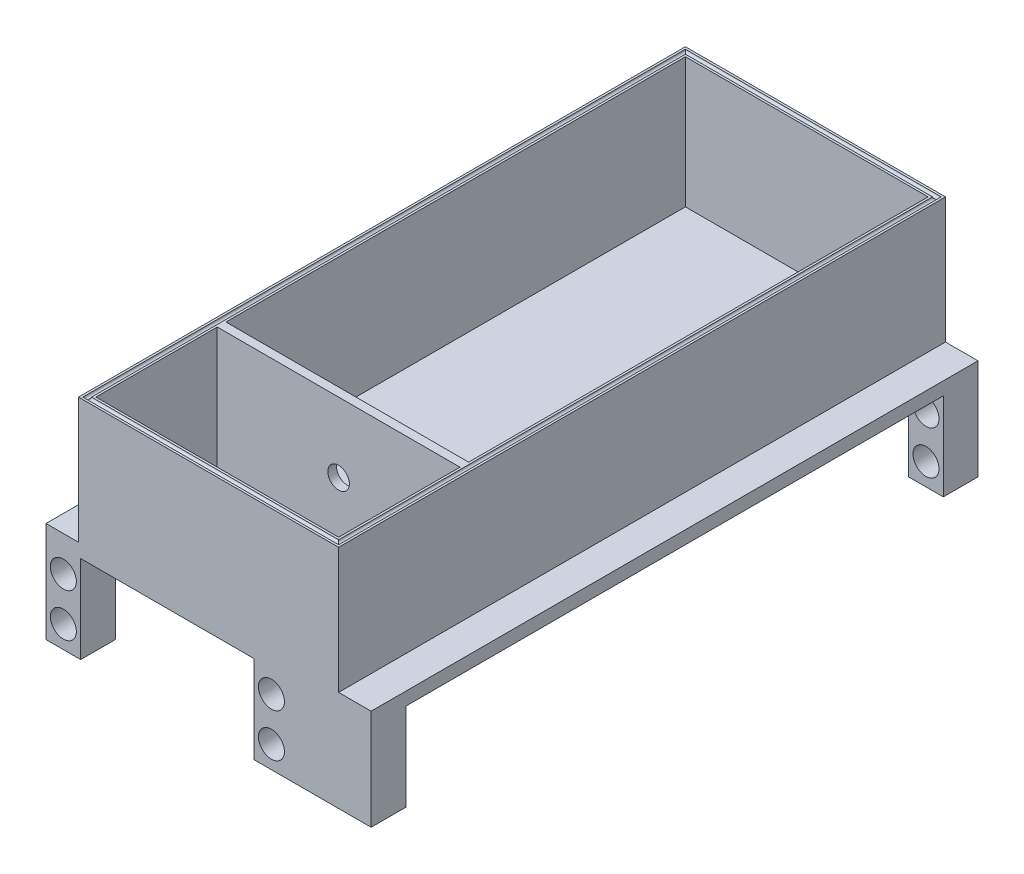
SolidWorks part; units mm, degrees
ref_plane "Front Plane" through (0, 0, 0) normal (0, 0, 1) x (1, 0, 0)
ref_plane "Top Plane" through (0, 0, 0) normal (0, 1, 0) x (1, 0, 0)
ref_plane "Right Plane" through (0, 0, 0) normal (1, 0, 0) x (0, 0, -1)
sketch "Sketch1" plane through (0, 0, 0) normal (0, 1, 0) x (1, 0, 0)
  line L1 (-30, 55) -> (30, 55)
  line L2 (-30, 55) -> (-30, -55)
  line L3 (-30, -55) -> (30, -55)
  line L4 (30, 55) -> (30, -55)
  line L5 (-30, 55) -> (30, -55) construction
  line L6 (-30, -55) -> (30, 55) construction
  point P0 (0, 0)
  dimension "D1" = 110
  dimension "D2" = 60
extrude "Boss-Extrude1" add sketch "Sketch1" along normal blind 2
sketch "Sketch2" plane through (0, 2, 0) normal (0, 1, 0) x (1, 0, 0)
  line L0 (-28, 53) -> (-28, -53)
  line L1 (-28, -53) -> (28, -53)
  line L2 (28, -53) -> (28, 53)
  line L3 (28, 53) -> (-28, 53)
  line L4 (30, -55) -> (30, 55)
  line L5 (30, 55) -> (-30, 55)
  line L6 (-30, 55) -> (-30, -55)
  line L7 (-30, -55) -> (30, -55)
  line L8 (30, -55) -> (30, 55)
  line L9 (30, 55) -> (-30, 55)
  line L10 (-30, 55) -> (-30, -55)
  line L11 (-30, -55) -> (30, -55)
  dimension "D1" = 0
  dimension "D2" = 2
extrude "Boss-Extrude2" add sketch "Sketch2" along normal blind 30
sketch "Sketch3" plane through (0, 0, 0) normal (0, 1, 0) x (1, 0, 0)
  line L0 (-30, -55) -> (30, -55) construction
  line L1 (-30, -55) -> (30, -55)
  line L2 (-30, -55) -> (-30, -85)
  line L3 (-30, -85) -> (30, -85)
  line L4 (30, -55) -> (30, -85)
  line L5 (30, -55) -> (30, 55) construction
  line L6 (-30, 55) -> (-30, -55) construction
  dimension "D2" = 30
extrude "Boss-Extrude3" add sketch "Sketch3" along normal blind 2
sketch "Sketch4" plane through (0, 2, 0) normal (0, 1, 0) x (1, 0, 0)
  line L4 (-28, -55) -> (-30, -55)
  line L8 (-28, -57) -> (-28, -83)
  line L9 (-28, -83) -> (28, -83)
  line L10 (28, -83) -> (28, -57)
  line L11 (28, -57) -> (-28, -57)
  line L12 (-28, -55) -> (-28, -83)
  line L13 (-28, -83) -> (28, -83)
  line L14 (28, -83) -> (28, -55)
  line L16 (-30, -55) -> (-30, -85)
  line L17 (-30, -85) -> (30, -85)
  line L18 (30, -85) -> (30, -55)
  line L19 (30, -55) -> (-30, -55)
  line L20 (-30, -55) -> (-30, -85)
  line L21 (-30, -85) -> (30, -85)
  line L22 (30, -85) -> (30, -55)
  line L23 (30, -55) -> (28, -55)
  dimension "D1" = 2
  dimension "D2" = 0
extrude "Boss-Extrude4" add sketch "Sketch4" along normal blind 30
sketch "Sketch5" plane through (0, 0, 55) normal (0, 0, 1) x (1, 0, 0)
  circle A0 centre (0, 15.8909) radius 2.4868
extrude "Cut-Extrude1" cut sketch "Sketch5" against normal blind 30
sketch "Sketch6" plane through (0, 32, 0) normal (0, 1, 0) x (1, 0, 0)
  line L17 (-29, 54) -> (-29, -84)
  line L18 (-29, -84) -> (29, -84)
  line L19 (29, -84) -> (29, 54)
  line L22 (29, 54) -> (-29, 54)
  line L25 (-29, 54) -> (-29, -84)
  line L26 (-29, -84) -> (29, -84)
  line L27 (29, -84) -> (29, 54)
  line L30 (29, 54) -> (-29, 54)
  dimension "D1" = 1
sweep "Cut-Sweep1" cut path "Sketch6" circular profile diameter 1 parameters "D3"=1
sketch "Sketch43" plane through (0, 0, 0) normal (0, -1, 0) x (1, 0, 0)
  line L11 (30, -55) -> (37.5, -55)
  line L12 (37.5, -55) -> (37.5, 85)
  line L13 (37.5, 85) -> (30, 85)
  line L14 (-30, -55) -> (-37.5, -55)
  line L15 (-37.5, -55) -> (-37.5, 85)
  line L16 (-37.5, 85) -> (-30, 85)
  line L18 (-30, 55) -> (-30, -55)
  line L19 (-30, 55) -> (-30, 85)
  line L21 (30, -55) -> (30, 85)
  dimension "D1" = 7.5
  dimension "D2" = 7.5
extrude "Boss-Extrude7" add sketch "Sketch43" against normal blind 3 contours L13 L21 L11 L12 | L16 L19 L18 L14 L15
sketch "Sketch55" plane through (0, 0, 0) normal (0, -1, 0) x (1, 0, 0)
  line L0 (-37.5, 85) -> (37.5, 85) construction
  line L1 (-37.5, 85) -> (-29.5, 85)
  line L2 (-37.5, 85) -> (-37.5, 77)
  line L3 (-37.5, 77) -> (-29.5, 77)
  line L4 (-29.5, 85) -> (-29.5, 77)
  line L5 (10.5, 85) -> (37.5, 85)
  line L6 (10.5, 85) -> (10.5, 77)
  line L7 (10.5, 77) -> (37.5, 77)
  line L8 (37.5, 85) -> (37.5, 77)
  line L9 (37.5, -55) -> (-37.5, -55) construction
  line L10 (37.5, -55) -> (29.5, -55)
  line L11 (37.5, -55) -> (37.5, -47)
  line L12 (37.5, -47) -> (29.5, -47)
  line L13 (29.5, -55) -> (29.5, -47)
  line L14 (-10.5, -55) -> (-37.5, -55)
  line L15 (-10.5, -55) -> (-10.5, -47)
  line L16 (-10.5, -47) -> (-37.5, -47)
  line L17 (-37.5, -55) -> (-37.5, -47)
  line L18 (37.5, -55) -> (37.5, 85) construction
  line L19 (-37.5, -55) -> (-37.5, 85) construction
  dimension "D1" = 8
  dimension "D2" = 8
  dimension "D3" = 8
  dimension "D5" = 40
  dimension "D6" = 8
  dimension "D7" = 8
  dimension "D8" = 8
  dimension "D10" = 40
extrude "Boss-Extrude10" add sketch "Sketch55" along normal blind 20.2
sketch "Sketch56" plane through (0, 0, 85) normal (0, 0, 1) x (1, 0, 0)
  line L0 (-29.5, 0) -> (-37.5, 0) construction
  line L1 (-9.5, 0) -> (-9.5, -17.0658) construction
  line L2 (-29.5, -20.2) -> (-37.5, -20.2) construction
  line L3 (-33.5, -15.1) -> (-33.5, -20.2) construction
  line L4 (-33.5, -15.1) -> (-33.5, -5.1) construction
  line L5 (-33.5, -5.1) -> (-33.5, 0) construction
  line L6 (-29.5, 0) -> (10.5, 0) construction
  circle A0 centre (-33.5, -15.1) radius 3
  circle A1 centre (-33.5, -5.1) radius 3
  circle A2 centre (14.5, -15.1) radius 3
  circle A3 centre (14.5, -5.1) radius 3
  dimension "D1" = 6
  dimension "D2" = 6
  dimension "D3" = 10
extrude "Cut-Extrude3" cut sketch "Sketch56" against normal blind 20.2
sketch "Sketch59" plane through (0, 0, -55) normal (0, 0, -1) x (-1, 0, 0)
  line L0 (-29.5, 0) -> (-37.5, 0) construction
  line L1 (-9.5, 0) -> (-9.5, -20.2) construction
  line L2 (-29.5, -20.2) -> (-37.5, -20.2) construction
  line L3 (-33.5, 0) -> (-33.5, -5.1) construction
  line L4 (-33.5, -20.2) -> (-33.5, -15.1) construction
  line L5 (-29.5, 0) -> (10.5, 0) construction
  circle A0 centre (-33.5, -15.1) radius 3
  circle A1 centre (-33.5, -5.1) radius 3
  circle A2 centre (14.5, -5.1) radius 3
  circle A3 centre (14.5, -15.1) radius 3
  dimension "D2" = 6
  dimension "D3" = 6
  dimension "D1" = 10
extrude "Cut-Extrude4" cut sketch "Sketch59" against normal blind 20.2
